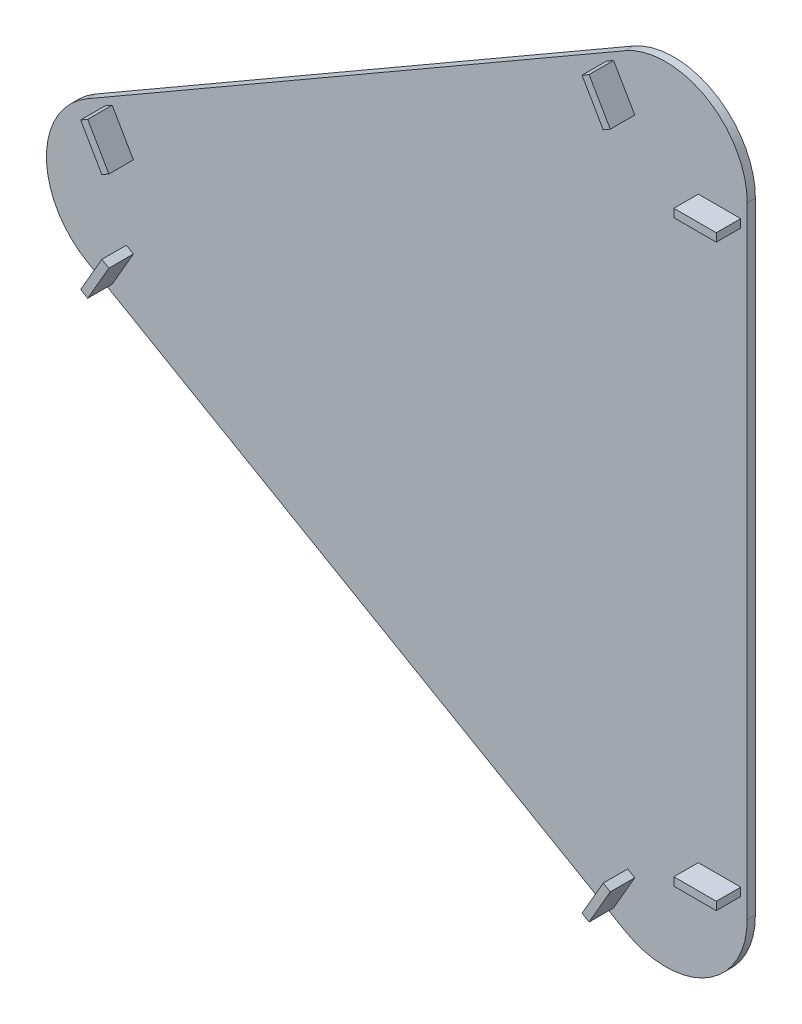
SolidWorks part; units mm, degrees
ref_plane "Front Plane" through (0, 0, 0) normal (0, 0, 1) x (1, 0, 0)
ref_plane "Top Plane" through (0, 0, 0) normal (0, 1, 0) x (1, 0, 0)
ref_plane "Right Plane" through (0, 0, 0) normal (1, 0, 0) x (0, 0, -1)
sketch "Sketch1" plane through (0, 0, 0) normal (0, 0, 1) x (1, 0, 0)
  line L0 (-20.7649, -83.0943) -> (-20.7649, -133.0943)
  line L2 (-46.7649, 71.9057) -> (-46.7649, 66.9057)
  line L4 (-20.7649, 71.9057) -> (-20.7649, 66.9057)
  line L5 (-23.1932, -133.0943) -> (-20.7649, -133.0943)
  line L6 (-46.7649, -133.0943) -> (-46.7649, -138.0943)
  line L7 (-24.2764, -138.0943) -> (-20.7649, -138.0943)
  line L8 (-20.7649, -133.0943) -> (-20.7649, -138.0943)
  line L10 (-20.7649, -78.0943) -> (-20.7649, -83.0943)
  line L12 (5.2351, -78.0943) -> (5.2351, -83.0943)
  line L13 (-20.7649, -283.0943) -> (5.2351, -283.0943)
  line L14 (-20.7649, -283.0943) -> (-20.7649, -288.0943)
  line L15 (-20.7649, -288.0943) -> (5.2351, -288.0943)
  line L16 (5.2351, -283.0943) -> (5.2351, -288.0943)
  line L17 (-20.7649, 116.9057) -> (-410.4763, -108.0943)
  line L18 (-410.4763, -108.0943) -> (-20.7649, -333.0943)
  line L19 (-20.7649, -333.0943) -> (-20.7649, 116.9057)
  line L20 (-59.736, 94.4057) -> (-64.0661, 91.9057)
  line L21 (-59.736, 94.4057) -> (-72.736, 116.9223)
  line L22 (-64.0661, 91.9057) -> (-77.0661, 114.4223)
  line L23 (-72.736, 116.9223) -> (-77.0661, 114.4223)
  line L24 (-241.6014, -10.5943) -> (-237.2712, -8.0943)
  line L27 (-254.6014, 11.9223) -> (-250.2712, 14.4223)
  line L28 (-193.97, 16.9057) -> (-189.6398, 19.4057)
  line L29 (-193.97, 16.9057) -> (-192.7558, 14.8027)
  line L30 (-189.6398, 19.4057) -> (-187.884, 16.3646)
  line L31 (-180.97, -5.611) -> (-176.6398, -3.111)
  line L32 (-367.175, -83.0943) -> (-371.5052, -85.5943)
  line L35 (-354.175, -105.611) -> (-358.5052, -108.111)
  line L36 (-371.5052, -130.5943) -> (-367.175, -133.0943)
  line L37 (-371.5052, -130.5943) -> (-384.5052, -153.111)
  line L38 (-367.175, -133.0943) -> (-380.175, -155.611)
  line L39 (-384.5052, -153.111) -> (-380.175, -155.611)
  line L40 (-193.97, -233.0943) -> (-189.6398, -235.5943)
  line L43 (-206.97, -255.611) -> (-202.6398, -258.111)
  line L44 (-241.6014, -205.5943) -> (-237.2712, -208.0943)
  line L45 (-241.6014, -205.5943) -> (-239.8456, -202.5532)
  line L46 (-237.2712, -208.0943) -> (-236.0571, -205.9913)
  line L47 (-228.6014, -183.0777) -> (-224.2712, -185.5777)
  line L48 (-64.0661, -308.0943) -> (-59.736, -310.5943)
  line L52 (-470.4763, -108.0943) -> (9.2351, 168.8672)
  line L53 (-470.4763, -108.0943) -> (9.2351, -385.0558)
  line L54 (9.2351, -385.0558) -> (9.2351, 168.8672)
  line L55 (-367.175, -83.0943) -> (-371.5052, -85.5943)
  line L56 (-367.175, -83.0943) -> (-380.175, -60.5777)
  line L57 (-371.5052, -85.5943) -> (-384.5052, -63.0777)
  line L58 (-380.175, -60.5777) -> (-384.5052, -63.0777)
  line L59 (-20.7649, 66.9057) -> (-20.7649, 71.9057)
  line L60 (-20.7649, 66.9057) -> (5.2351, 66.9057)
  line L61 (-20.7649, 71.9057) -> (5.2351, 71.9057)
  line L62 (5.2351, 66.9057) -> (5.2351, 71.9057)
  line L63 (-64.0661, -308.0943) -> (-59.736, -310.5943)
  line L64 (-64.0661, -308.0943) -> (-77.0661, -330.611)
  line L65 (-59.736, -310.5943) -> (-72.736, -333.111)
  line L66 (-77.0661, -330.611) -> (-72.736, -333.111)
  circle A0 centre (-150.6687, -108.0943) radius 129.9038 construction
  point P18 (-20.7649, -80.5943)
  point P23 (-20.7649, -108.0943)
  dimension "D1" = 26
  dimension "D2" = 5
  dimension "D3" = 5
  dimension "D4" = 26
  dimension "D5" = 26
  dimension "D6" = 5
  dimension "D8" = 26
  dimension "D9" = 5
  dimension "D10" = 5
  dimension "D12" = 45
  dimension "D13" = 45
  dimension "D14" = 26
  dimension "D15" = 5
  dimension "D17" = 26
  dimension "D18" = 5
  dimension "D20" = 26
  dimension "D21" = 5
  dimension "D24" = 26
  dimension "D25" = 5
  dimension "D26" = 45
  dimension "D27" = 26
  dimension "D28" = 5
  dimension "D30" = 26
  dimension "D31" = 5
  dimension "D36" = 30
  dimension "D37" = 30
  dimension "D38" = 30
  dimension "D39" = 26
  dimension "D40" = 26
  dimension "D41" = 26
extrude "Boss-Extrude1" add sketch "Sketch1" along normal blind 5 contours L18 L19 L14 L7 L6 L5 L0 L10 L2 L17 L30 L31 L29 L35 L45 L47 L46 | L53 L54 L52 L43 L18 L38 L39 L37 L17 L27 L22 L23 L21 L19 L4 L12 L0 L8 L13 L16 L15 region at (-150.6687, -108.0943, 0) region at (-226.9567, 24.0405, 0)
fillet "Fillet1" radius 50 3 edges at (9.2351, 168.8672, 2.5) (-470.4763, -108.0943, 2.5) (9.2351, -385.0558, 2.5)
extrude "Boss-Extrude2" add sketch "Sketch1<5>" along normal blind 20 contours L60 L62 L61 L4 | L21 L23 L22 L17 | L56 L58 L57 L17 | L37 L39 L38 L18 | L64 L66 L65 L18 | L16 L13 L14 L15 region at (-7.7649, 69.4057, 0) region at (-7.7649, -285.5943, 0) region at (-68.4011, 104.414, 0) region at (-68.4011, -320.6027, 0) region at (-375.8401, -73.086, 0) region at (-375.8401, -143.1027, 0)
sketch "Sketch1<5>" plane through (0, 0, 0) normal (0, 0, 1) x (1, 0, 0) same geometry as "Sketch1"
